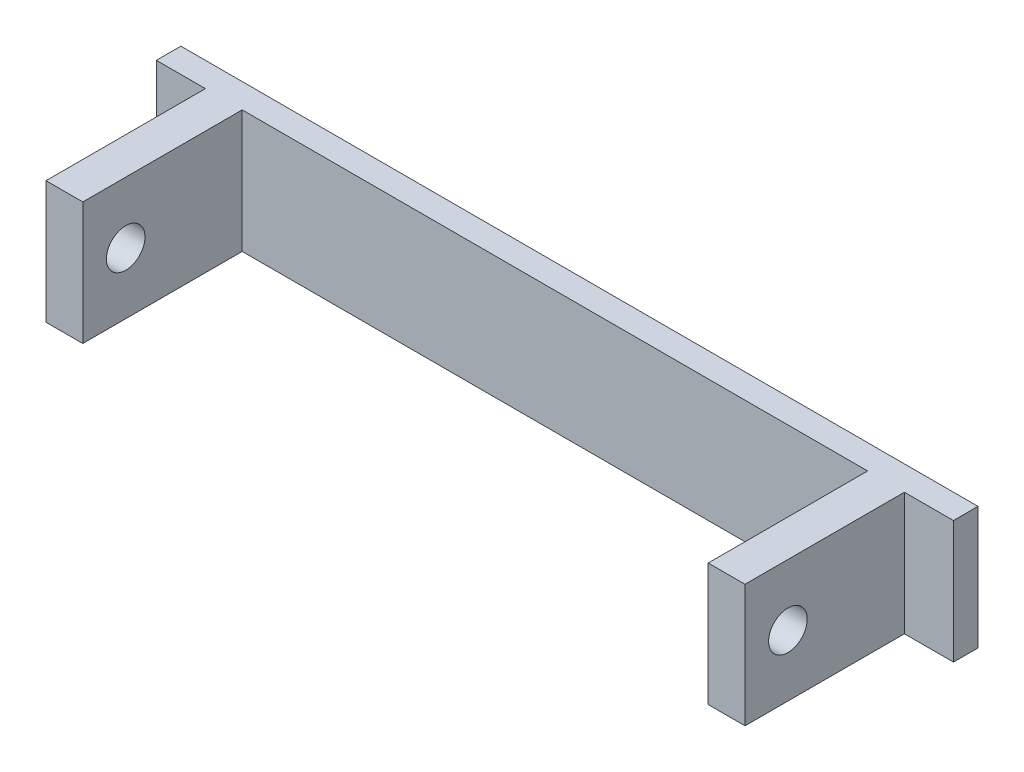
SolidWorks part; units mm, degrees
ref_plane "前视基准面" through (0, 0, 0) normal (0, 0, 1) x (1, 0, 0)
ref_plane "上视基准面" through (0, 0, 0) normal (0, 1, 0) x (1, 0, 0)
ref_plane "右视基准面" through (0, 0, 0) normal (1, 0, 0) x (0, 0, -1)
sketch "草图1" plane through (0, 0, 0) normal (0, 0, 1) x (1, 0, 0)
  line L1 (-32.5, -5) -> (32.5, -5)
  line L2 (-32.5, -5) -> (-32.5, 5)
  line L3 (-32.5, 5) -> (32.5, 5)
  line L4 (32.5, -5) -> (32.5, 5)
  line L5 (-32.5, -5) -> (32.5, 5) construction
  line L6 (-32.5, 5) -> (32.5, -5) construction
  point P0 (0, 0)
  dimension "D1" = 10
  dimension "D2" = 65
extrude "凸台-拉伸1" add sketch "草图1" along normal blind 2
sketch "草图2" plane through (0, 0, 2) normal (0, 0, 1) x (1, 0, 0)
  line L0 (32.5, 5) -> (-32.5, 5) construction
  line L1 (-28.5, 5) -> (-25.5, 5)
  line L2 (-28.5, 5) -> (-28.5, -5)
  line L3 (-28.5, -5) -> (-25.5, -5)
  line L4 (-25.5, 5) -> (-25.5, -5)
  line L5 (-32.5, -5) -> (32.5, -5) construction
  line L6 (32.5, -5) -> (32.5, 5) construction
  line L7 (25.5, 5) -> (28.5, 5)
  line L8 (25.5, 5) -> (25.5, -5)
  line L9 (25.5, -5) -> (28.5, -5)
  line L10 (28.5, 5) -> (28.5, -5)
  line L11 (-32.5, 5) -> (-32.5, -5) construction
  dimension "D1" = 3
  dimension "D2" = 4
  dimension "D3" = 3
  dimension "D4" = 4
extrude "凸台-拉伸2" add sketch "草图2" along normal blind 13
sketch "草图3" plane through (28.5, 0, 0) normal (1, 0, 0) x (0, 0, -1)
  line L2 (-15, 0) -> (-9.2904, 0) construction
  line L3 (-15, -5) -> (-15, 5) construction
  line L4 (0, -5) -> (0, 5) construction
  circle A0 centre (-11.5, 0) radius 1.575
  point P2 (0, 0)
  dimension "D1" = 3.15
  dimension "D2" = 11.5
extrude "切除-拉伸1" cut sketch "草图3" against normal up to surface (57 mm away) up to face at (-28.5, 0, 8.5)
